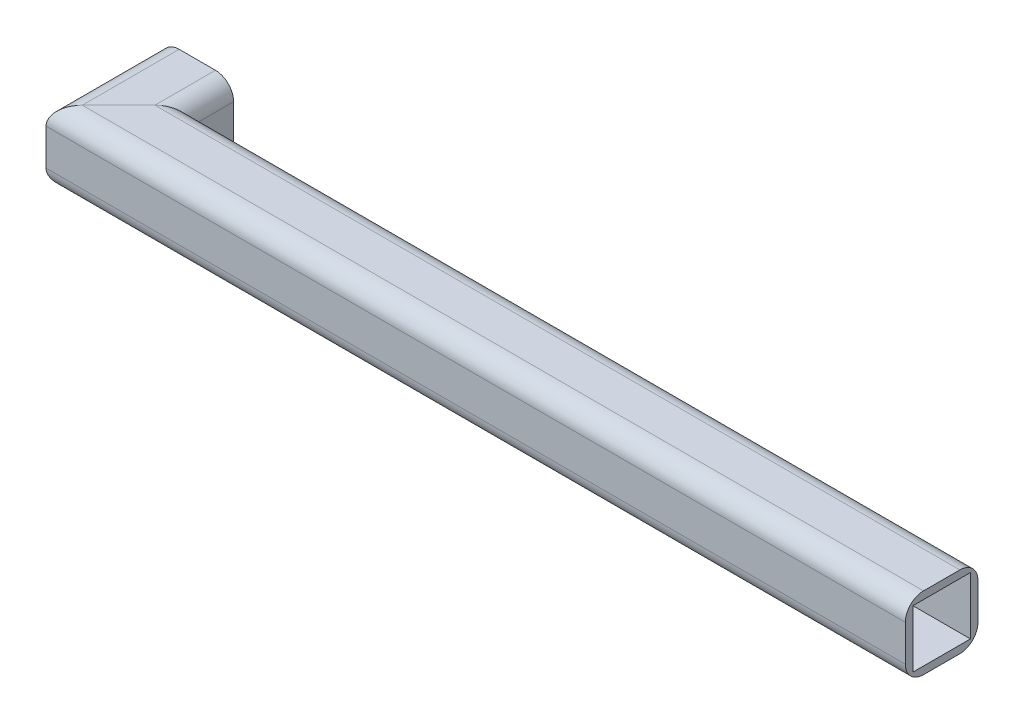
SolidWorks part; units mm, degrees
ref_plane "Front Plane" through (0, 0, 0) normal (0, 0, 1) x (1, 0, 0)
ref_plane "Top Plane" through (0, 0, 0) normal (0, 1, 0) x (1, 0, 0)
ref_plane "Right Plane" through (0, 0, 0) normal (1, 0, 0) x (0, 0, -1)
sketch3d "3DSketch3"
  line L0 (60.325, 60.325, 0) -> (60.325, 60.325, 165.1)
  line L5 (60.325, 60.325, 165.1) -> (1787.525, 60.325, 165.1)
  point P0 (0, 0, 0)
  point P11 (0, 0, 0)
  dimension "D3" = 165.1
  dimension "D4" = 1727.2
sketch "Sketch12" plane through (0, 0, 0) normal (0, 0, 1) x (1, 0, 0)
  line L0 (120.65, 0) -> (120.65, 120.65)
  line L6 (22.225, 136.525) -> (98.425, 136.525)
  line L7 (120.65, 120.65) -> (0, 120.65)
  line L8 (0, 120.65) -> (0, 0)
  line L9 (0, 0) -> (120.65, 0)
  line L10 (-15.875, 98.425) -> (-15.875, 22.225)
  line L11 (22.225, -15.875) -> (98.425, -15.875)
  line L12 (136.525, 98.425) -> (136.525, 22.225)
  line L13 (-15.875, 136.525) -> (136.525, -15.875) construction
  line L14 (-15.875, -15.875) -> (136.525, 136.525) construction
  arc A7 (-15.875, 22.225) -> (22.225, -15.875) centre (22.225, 22.225) ccw
  arc A8 (98.425, -15.875) -> (136.525, 22.225) centre (98.425, 22.225) ccw
  arc A9 (98.425, 136.525) -> (136.525, 98.425) centre (98.425, 98.425) cw
  arc A10 (22.225, 136.525) -> (-15.875, 98.425) centre (22.225, 98.425) ccw
  point P0 (60.325, 60.325)
  point P6 (60.325, 60.325)
  dimension "D3" = 152.4
  dimension "D5" = 38.1
  dimension "D1" = 120.65
  dimension "D2" = 120.65
  dimension "D4" = 152.4
sweep "Sweep1" add profiles "Sketch12" path "3DSketch3"
